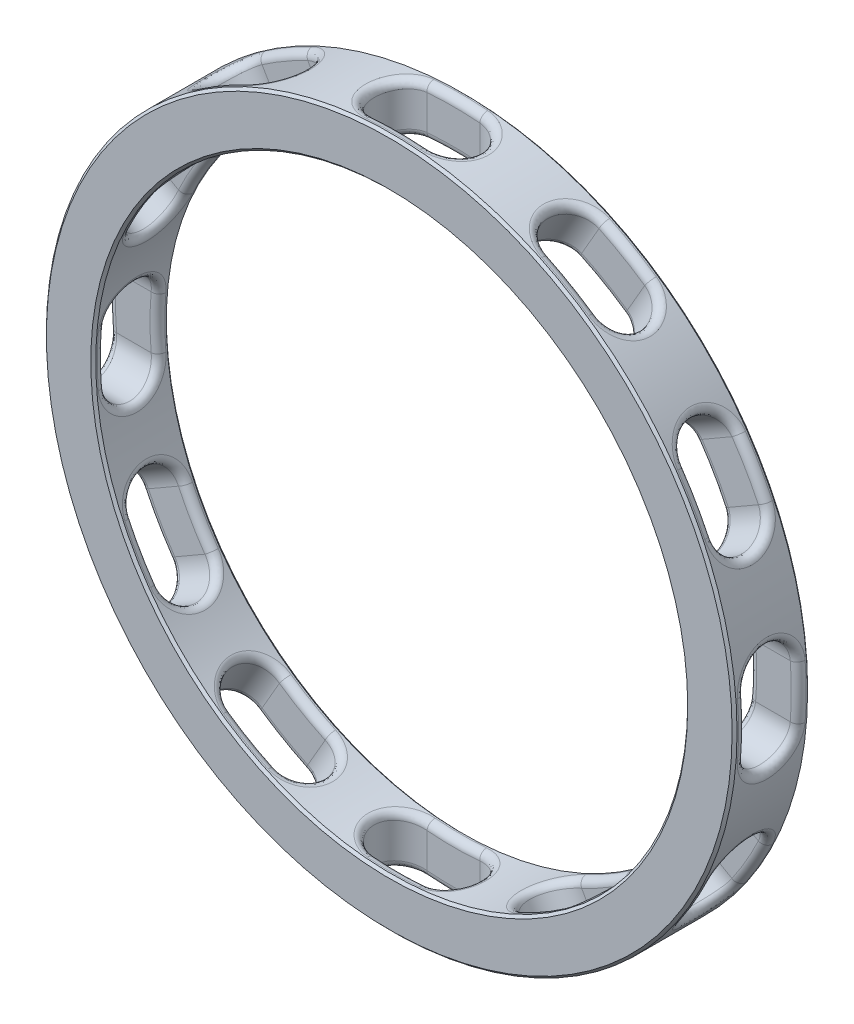
SolidWorks part; units mm, degrees
ref_plane "Front Plane" through (0, 0, 0) normal (0, 0, 1) x (1, 0, 0)
ref_plane "Top Plane" through (0, 0, 0) normal (0, 1, 0) x (1, 0, 0)
ref_plane "Right Plane" through (0, 0, 0) normal (1, 0, 0) x (0, 0, -1)
sketch "Sketch2" plane through (0, 0, 0) normal (0, 0, 1) x (1, 0, 0)
  circle A0 centre (0, 0) radius 35
  dimension "D1" = 70
extrude "Extrude-Thin1" add sketch "Sketch2" along normal mid plane 7.65 thin thin type one direction reverse wall 5
sketch "Sketch3" plane through (0, 0, 0) normal (0, 1, 0) x (1, 0, 0)
  line L0 (2.675, 0) -> (-2.675, 0) construction
  line L1 (2.675, -2.675) -> (-2.675, -2.675)
  line L2 (2.675, 2.675) -> (-2.675, 2.675)
  arc A0 (2.675, -2.675) -> (2.675, 2.675) centre (2.675, 0) ccw
  arc A1 (-2.675, 2.675) -> (-2.675, -2.675) centre (-2.675, 0) ccw
  point P2 (0, 0)
  dimension "D1" = 5.35
  dimension "D2" = 5.35
extrude "Cut-Extrude1" cut sketch "Sketch3" against normal through all
fillet "Fillet1" radius 0.75 8 edges at (0, -35, 2.675) (-5.3308, -34.5917, 0.3197) (0, -35, -2.675) (0, -30, 2.675) (-5.3304, -29.5227, 0.3233) (0, -30, -2.675) (5.3308, -34.5917, -0.3197) (5.3304, -29.5227, -0.3233)
chamfer "Chamfer1" distance 0.25 angle 45 4 edges at (35, 0, -3.825) (35, 0, 3.825) (30, 0, -3.825) (30, 0, 3.825)
pattern_circular "CirPattern1" count 12 over 360 about axis through (0, 0, 3.825) along (0, 0, -1) of "Cut-Extrude1", "Fillet1"
